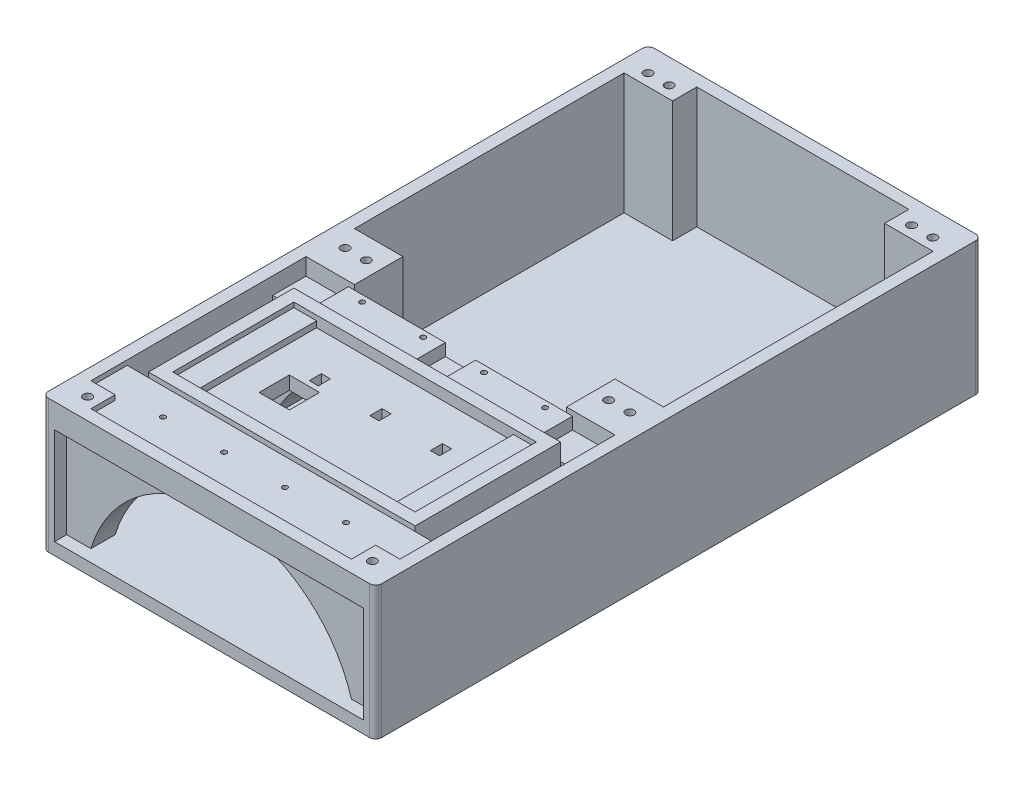
SolidWorks part; units mm, degrees
ref_plane "Front Plane" through (0, 0, 0) normal (0, 0, 1) x (1, 0, 0)
ref_plane "Top Plane" through (0, 0, 0) normal (0, 1, 0) x (1, 0, 0)
ref_plane "Right Plane" through (0, 0, 0) normal (1, 0, 0) x (0, 0, -1)
sketch "Sketch1" plane through (0, 0, 0) normal (0, 1, 0) x (1, 0, 0)
  line L1 (0, 0) -> (139.7, 0)
  line L2 (0, 0) -> (0, 254)
  line L3 (0, 254) -> (139.7, 254)
  line L4 (139.7, 0) -> (139.7, 254)
  dimension "D1" = 254
  dimension "D2" = 139.7
extrude "Base" add sketch "Sketch1" along normal blind 5.08
sketch "Sketch2" plane through (0, 5.08, 0) normal (0, 1, 0) x (1, 0, 0)
  line L1 (0, 254) -> (139.7, 254)
  line L2 (0, 254) -> (0, 0)
  line L3 (0, 0) -> (139.7, 0)
  line L4 (139.7, 254) -> (139.7, 0)
  line L5 (5.08, 248.92) -> (134.62, 248.92)
  line L6 (5.08, 248.92) -> (5.08, 5.08)
  line L7 (5.08, 5.08) -> (134.62, 5.08)
  line L8 (134.62, 248.92) -> (134.62, 5.08)
  line M9 (0, 254) -> (0, 0)
  line M10 (0, 0) -> (139.7, 0)
  line M11 (139.7, 0) -> (139.7, 254)
  line M12 (139.7, 254) -> (0, 254)
  dimension "D1" = 5.08
  dimension "D2" = 5.08
  dimension "D3" = 5.08
  dimension "D4" = 5.08
extrude "Walls" add sketch "Sketch2" along normal blind 50.8 contours L5 L8 L7 L6 M12 M9 M10 M11 region at (69.85, 5.08, -251.1012)
sketch "Sketch3" [suppressed] plane through (0, 55.88, 0) normal (0, 1, 0) x (1, 0, 0)
  line L1 (5.08, 248.92) -> (134.62, 248.92)
  line L2 (5.08, 248.92) -> (5.08, 5.08)
  line L3 (5.08, 5.08) -> (134.62, 5.08)
  line L4 (134.62, 248.92) -> (134.62, 5.08)
  line L5 (2.54, 251.46) -> (137.16, 251.46)
  line L6 (2.54, 251.46) -> (2.54, 2.54)
  line L7 (2.54, 2.54) -> (137.16, 2.54)
  line L8 (137.16, 251.46) -> (137.16, 2.54)
  dimension "D1" = 2.54
  dimension "D2" = 2.54
  dimension "D3" = 2.54
  dimension "D4" = 2.54
sketch "Sketch5" plane through (0, 5.08, 0) normal (0, 1, 0) x (1, 0, 0)
  line L0 (5.08, 5.08) -> (5.08, 248.92) construction
  line L1 (5.08, 105.41) -> (134.62, 105.41)
  line L2 (5.08, 105.41) -> (5.08, 16.51)
  line L3 (5.08, 16.51) -> (134.62, 16.51)
  line L4 (134.62, 105.41) -> (134.62, 16.51)
  line L6 (134.62, 248.92) -> (134.62, 5.08) construction
  point P8 (134.62, 60.96)
  dimension "D1" = 60.96
  dimension "D2" = 88.9
extrude "Button Support" add sketch "Sketch5" along normal blind 48.768
ref_plane "Plane1" through (0, 0, -60.96) normal (0, 0, 1) x (1, 0, 0)
sketch "Sketch6" plane through (0, 53.848, 0) normal (0, 1, 0) x (1, 0, 0)
  line L0 (0, 0) -> (139.7, 0) construction
  line L1 (19.05, 86.36) -> (120.65, 86.36)
  line L2 (19.05, 86.36) -> (19.05, 35.56)
  line L3 (19.05, 35.56) -> (120.65, 35.56)
  line L4 (120.65, 86.36) -> (120.65, 35.56)
  line L5 (125.73, 91.44) -> (13.97, 91.44)
  line L6 (125.73, 91.44) -> (125.73, 30.48)
  line L7 (125.73, 30.48) -> (13.97, 30.48)
  line L8 (13.97, 91.44) -> (13.97, 30.48)
  line L9 (134.62, 105.41) -> (5.08, 105.41) construction
  point P8 (69.85, 91.44)
  point P9 (69.85, 86.36)
  point P10 (120.65, 60.96)
  point P11 (125.73, 60.96)
  point P16 (69.85, 105.41)
  dimension "D1" = 50.8
  dimension "D2" = 60.96
  dimension "D3" = 101.6
  dimension "D4" = 5.08
  dimension "D5" = 5.08
extrude "Boss-Extrude4" add sketch "Sketch6" along normal blind 2.032
sketch "Sketch7" plane through (0, 53.848, 0) normal (0, 1, 0) x (1, 0, 0)
  line L0 (19.05, 35.56) -> (120.65, 35.56) construction
  line L1 (28.575, 35.56) -> (111.125, 35.56)
  line L2 (28.575, 35.56) -> (28.575, 86.36)
  line L3 (28.575, 86.36) -> (111.125, 86.36)
  line L4 (111.125, 35.56) -> (111.125, 86.36)
  line L5 (120.65, 86.36) -> (19.05, 86.36) construction
  point P8 (69.85, 86.36)
  point P9 (69.85, 35.56)
  dimension "D1" = 82.55
  dimension "D2" = 50.8
extrude "Force Sensor Cutout" cut sketch "Sketch7" against normal blind 2.54
sketch "Sketch4" plane through (0, 0, 0) normal (0, 0, 1) x (1, 0, 0)
  line L0 (0, 0) -> (139.7, 0) construction
  line L1 (5.08, 45.72) -> (134.62, 45.72)
  line L2 (5.08, 45.72) -> (5.08, 5.08)
  line L3 (5.08, 5.08) -> (134.62, 5.08)
  line L4 (134.62, 45.72) -> (134.62, 5.08)
  line L5 (0, 55.88) -> (0, 0) construction
  line L6 (139.7, 55.88) -> (139.7, 0) construction
  line L7 (0, 55.88) -> (139.7, 55.88) construction
  dimension "D1" = 5.08
  dimension "D2" = 5.08
  dimension "D3" = 5.08
  dimension "D4" = 10.16
extrude "Bottom Cut" cut sketch "Sketch4" against normal blind 139.7
sketch "Sketch8" plane through (0, 51.308, 0) normal (0, 1, 0) x (1, 0, 0)
  line L0 (120.65, 86.36) -> (19.05, 86.36) construction
  line L1 (71.628, 65.623) -> (75.438, 65.623)
  line L2 (71.628, 65.623) -> (71.628, 70.703)
  line L3 (71.628, 70.703) -> (75.438, 70.703)
  line L4 (75.438, 65.623) -> (75.438, 70.703)
  line L5 (120.65, 35.56) -> (120.65, 86.36) construction
  line L6 (97.028, 65.623) -> (97.028, 70.703)
  line L7 (97.028, 65.623) -> (100.838, 65.623)
  line L8 (100.838, 65.623) -> (100.838, 70.703)
  line L9 (97.028, 70.703) -> (100.838, 70.703)
  line L10 (46.228, 65.623) -> (46.228, 70.703)
  line L11 (46.228, 65.623) -> (50.038, 65.623)
  line L12 (50.038, 65.623) -> (50.038, 70.703)
  line L13 (46.228, 70.703) -> (50.038, 70.703)
  dimension "D1" = 15.657
  dimension "D2" = 45.212
  dimension "D3" = 3.81
  dimension "D4" = 5.08
  dimension "D5" = 2
  dimension "D6" = 2
extrude "Haptic Wire Holes" cut sketch "Sketch8" against normal up to surface (5.588 mm away) up to face at (69.85, 45.72, -60.96)
sketch "Sketch9" plane through (0, 51.308, 0) normal (0, 1, 0) x (1, 0, 0)
  line L0 (120.65, 86.36) -> (19.05, 86.36) construction
  line L1 (52.705, 63.5) -> (40.005, 63.5)
  line L2 (52.705, 63.5) -> (52.705, 50.8)
  line L3 (52.705, 50.8) -> (40.005, 50.8)
  line L4 (40.005, 63.5) -> (40.005, 50.8)
  line L5 (28.575, 86.36) -> (28.575, 35.56) construction
  dimension "D1" = 12.7
  dimension "D2" = 12.7
  dimension "D3" = 22.86
  dimension "D4" = 11.43
extrude "Force Sensor Hole" cut sketch "Sketch9" against normal up to surface (5.588 mm away) up to face at (48.133, 45.72, -68.163)
sketch "Sketch10" plane through (0, 53.848, 0) normal (0, 1, 0) x (1, 0, 0)
  line L0 (5.08, 16.51) -> (134.62, 16.51) construction
  line L1 (134.62, 105.41) -> (134.62, 16.51) construction
  line L2 (-4.4704, 60.96) -> (4.4704, 60.96) construction
  circle A0 centre (108.0186, 19.2295) radius 1.0795
  circle A4 centre (82.4261, 19.2295) radius 1.0795
  circle A5 centre (56.9186, 19.2295) radius 1.0795
  circle A6 centre (31.3261, 19.2295) radius 1.0795
  circle A7 centre (31.3261, 102.6905) radius 1.0795
  circle A8 centre (56.9186, 102.6905) radius 1.0795
  circle A9 centre (82.4261, 102.6905) radius 1.0795
  circle A10 centre (108.0186, 102.6905) radius 1.0795
  dimension "D1" = 2.159
  dimension "D2" = 2.7195
  dimension "D3" = 26.6014
  dimension "D5" = 25.5925
  dimension "D6" = 25.5075
  dimension "D4" = 25.5925
extrude "NeoPixel Holes" cut sketch "Sketch10" against normal up to surface (8.128 mm away) up to face at (46.355, 45.72, -57.15)
sketch "Sketch18" plane through (0, 53.848, 0) normal (0, 1, 0) x (1, 0, 0)
  line L0 (134.62, 248.92) -> (134.62, 5.08) construction
  line L1 (125.73, 91.44) -> (134.62, 91.44)
  line L2 (125.73, 91.44) -> (125.73, 30.48)
  line L3 (125.73, 30.48) -> (134.62, 30.48)
  line L4 (134.62, 91.44) -> (134.62, 30.48)
  line L5 (5.08, 105.41) -> (5.08, 16.51) construction
  line L6 (13.97, 91.44) -> (5.08, 91.44)
  line L7 (13.97, 91.44) -> (13.97, 30.48)
  line L8 (13.97, 30.48) -> (5.08, 30.48)
  line L9 (5.08, 91.44) -> (5.08, 30.48)
  line L10 (13.97, 30.48) -> (125.73, 30.48) construction
extrude "Neopixel Wire Side Holes" cut sketch "Sketch18" against normal up to next
sketch "Sketch11" plane through (0, 0, -16.51) normal (0, 0, 1) x (1, 0, 0)
  line L1 (5.08, 53.848) -> (134.62, 53.848)
  line L2 (5.08, 53.848) -> (5.08, 45.72)
  line L3 (5.08, 45.72) -> (134.62, 45.72)
  line L4 (134.62, 53.848) -> (134.62, 45.72)
extrude "Boss-Extrude5" add sketch "Sketch11" along normal up to next
sketch "Sketch12" plane through (0, 5.08, 0) normal (0, 1, 0) x (1, 0, 0)
  line L0 (139.7, 254) -> (0, 254) construction
  line L1 (134.62, 248.92) -> (114.3, 248.92)
  line L2 (134.62, 248.92) -> (134.62, 238.76)
  line L3 (134.62, 238.76) -> (114.3, 238.76)
  line L4 (114.3, 248.92) -> (114.3, 238.76)
  line L5 (139.7, 0) -> (139.7, 254) construction
  line L7 (5.08, 248.92) -> (25.4, 248.92)
  line L8 (5.08, 248.92) -> (5.08, 238.76)
  line L9 (5.08, 238.76) -> (25.4, 238.76)
  line L10 (25.4, 248.92) -> (25.4, 238.76)
  line L11 (134.62, 105.41) -> (114.3, 105.41)
  line L12 (134.62, 105.41) -> (134.62, 125.73)
  line L13 (134.62, 125.73) -> (114.3, 125.73)
  line L14 (114.3, 105.41) -> (114.3, 125.73)
  line L15 (5.08, 105.41) -> (25.4, 105.41)
  line L16 (5.08, 105.41) -> (5.08, 125.73)
  line L17 (5.08, 125.73) -> (25.4, 125.73)
  line L18 (25.4, 105.41) -> (25.4, 125.73)
  dimension "D1" = 15.24
  dimension "D2" = 25.4
  dimension "D3" = 20.32
extrude "Mounting Struts" add sketch "Sketch12" along normal up to surface (50.8 mm away) up to face at (69.85, 55.88, -127)
sketch "Sketch19" plane through (0, 53.848, 0) normal (0, 1, 0) x (1, 0, 0)
  line L0 (25.4, 105.41) -> (5.08, 105.41) construction
  line L1 (76.2, 105.41) -> (63.5, 105.41)
  line L2 (76.2, 105.41) -> (76.2, 91.44)
  line L3 (76.2, 91.44) -> (63.5, 91.44)
  line L4 (63.5, 105.41) -> (63.5, 91.44)
  line L5 (22.86, 105.41) -> (5.08, 105.41)
  line L6 (22.86, 105.41) -> (22.86, 91.44)
  line L7 (22.86, 91.44) -> (5.08, 91.44)
  line L8 (5.08, 105.41) -> (5.08, 91.44)
  line L9 (5.08, 105.41) -> (5.08, 91.44) construction
  line L10 (114.3, 105.41) -> (25.4, 105.41) construction
  line L11 (134.62, 105.41) -> (116.84, 105.41)
  line L12 (134.62, 105.41) -> (134.62, 91.44)
  line L13 (134.62, 91.44) -> (116.84, 91.44)
  line L14 (116.84, 105.41) -> (116.84, 91.44)
  line L15 (125.73, 91.44) -> (13.97, 91.44) construction
  point P19 (69.85, 105.41)
  point P20 (69.85, 105.41)
  dimension "D1" = 12.7
  dimension "D2" = 17.78
extrude "NeoPixel solder gap" cut sketch "Sketch19" against normal blind 5.08
sketch "Sketch13" plane through (0, 55.88, 0) normal (0, 1, 0) x (1, 0, 0)
  line L0 (139.7, 254) -> (0, 254) construction
  line L1 (139.7, 0) -> (139.7, 254) construction
  circle A0 centre (120.65, 243.713) radius 1.778
  circle A1 centre (19.05, 243.713) radius 1.778
  circle A2 centre (120.65, 116.713) radius 1.778
  circle A3 centre (19.05, 116.713) radius 1.778
  dimension "D1" = 3.556
  dimension "D2" = 10.287
  dimension "D3" = 19.05
  dimension "D4" = 101.6
  dimension "D5" = 127
extrude "Panel Mounting Holes" cut sketch "Sketch13" against normal blind 12.7
sketch "Sketch14" plane through (0, 53.848, 0) normal (0, 1, 0) x (1, 0, 0)
  line L1 (134.62, 5.08) -> (124.46, 5.08)
  line L2 (134.62, 5.08) -> (134.62, 15.24)
  line L3 (134.62, 15.24) -> (124.46, 15.24)
  line L4 (124.46, 5.08) -> (124.46, 15.24)
  line L5 (5.08, 5.08) -> (15.24, 5.08)
  line L6 (5.08, 5.08) -> (5.08, 15.24)
  line L7 (5.08, 15.24) -> (15.24, 15.24)
  line L8 (15.24, 5.08) -> (15.24, 15.24)
  dimension "D1" = 10.16
  dimension "D2" = 10.16
extrude "Boss-Extrude6" add sketch "Sketch14" along normal up to surface and the other way up to surface up to face at (19.05, 55.88, -241.935) other way up to face at (69.85, 5.08, -148.59)
sketch "Sketch17" plane through (0, 55.88, 0) normal (0, 1, 0) x (1, 0, 0)
  line L0 (139.7, 0) -> (139.7, 254) construction
  line L1 (0, -30.734) -> (0, 30.734) construction
  circle A0 centre (129.54, 243.713) radius 1.778
  circle A1 centre (10.16, 243.713) radius 1.778
  circle A2 centre (10.16, 116.713) radius 1.778
  circle A3 centre (129.54, 116.713) radius 1.778
  circle A4 centre (129.54, 8.763) radius 1.778
  circle A5 centre (10.16, 8.763) radius 1.778
  circle A7 centre (120.65, 116.713) radius 1.778 construction
  circle A8 centre (19.05, 116.713) radius 1.778 construction
  circle A9 centre (19.05, 243.713) radius 1.778 construction
  circle A10 centre (120.65, 243.713) radius 1.778 construction
  dimension "D1" = 3.556
  dimension "D2" = 10.16
  dimension "D3" = 10.16
  dimension "D4" = 127
  dimension "D5" = 107.95
extrude "Front Mounting Holes" cut sketch "Sketch17" against normal blind 12.7
sketch "Sketch20" plane through (0, 0, -5.08) normal (0, 0, 1) x (1, 0, 0)
  line L0 (134.62, 45.72) -> (5.08, 45.72) construction
  line L1 (15.24, 5.08) -> (15.24, 45.72)
  line L2 (25.4, 45.72) -> (5.08, 45.72) construction
  line L3 (15.24, 45.72) -> (124.46, 45.72)
  line L4 (124.46, 45.72) -> (124.46, 5.08)
  arc A0 (124.46, 5.08) -> (15.24, 5.08) centre (69.85, -11.2911) ccw
  point P3 (69.85, 45.72)
  line M3 (124.46, 45.72) -> (124.46, 5.08)
extrude "Bottom Arch" add sketch "Sketch20" against normal up to surface (10.16 mm away) contours A0 L3 L1 | A0 L3 M3 region at (111.9431, 34.9545, -5.08) region at (27.7569, 34.9545, -5.08) up to face at (10.16, 25.4, -15.24)
sketch "Sketch21" plane through (0, 0, -105.41) normal (0, 0, 1) x (1, 0, 0)
  line L1 (5.08, 5.08) -> (5.08, 45.72)
  line L3 (5.08, 45.72) -> (134.62, 45.72)
  line L4 (134.62, 45.72) -> (134.62, 5.08)
  line L5 (114.3, 45.72) -> (25.4, 45.72) construction
  arc A0 (134.62, 5.08) -> (5.08, 5.08) centre (69.85, -27.3504) ccw
  point P3 (0, 0)
  point P6 (0, 0)
  point P7 (69.85, 45.085)
  dimension "D1" = 0.635
extrude "Boss-Extrude11" add sketch "Sketch21" along normal up to surface (13.97 mm away) up to face at (130.175, 47.244, -91.44)
fillet "Fillet1" radius 2.54 4 edges at (0, 27.94, 0) (139.7, 27.94, 0) (0, 27.94, -254) (139.7, 27.94, -254)
equation "\"Arrow Height\"= 1.5in"
equation "\"Button Height\"= 2in"
equation "\"Button Width\"= 4in"
equation "\"Haptic Diameter\"= 10mm"
equation "\"Haptic Thickness\"= 2.7mm"
equation "\"Arrow Spacing\"= 1in"
equation "\"Arrow Width\"= 1in"
equation "\"Haptic Wire Angle\"= 63.43"
equation "\"Haptic Wire Width\"= .1in"
equation "\"Haptic Wire Height\"= .15in"
equation "\"Mounting Bolt Hole Diameter\"= .14in"
equation "\"D1@Sketch13\"=\"Mounting Bolt Hole Diameter\""
equation "\"D1@Sketch17\"=\"Mounting Bolt Hole Diameter\""
